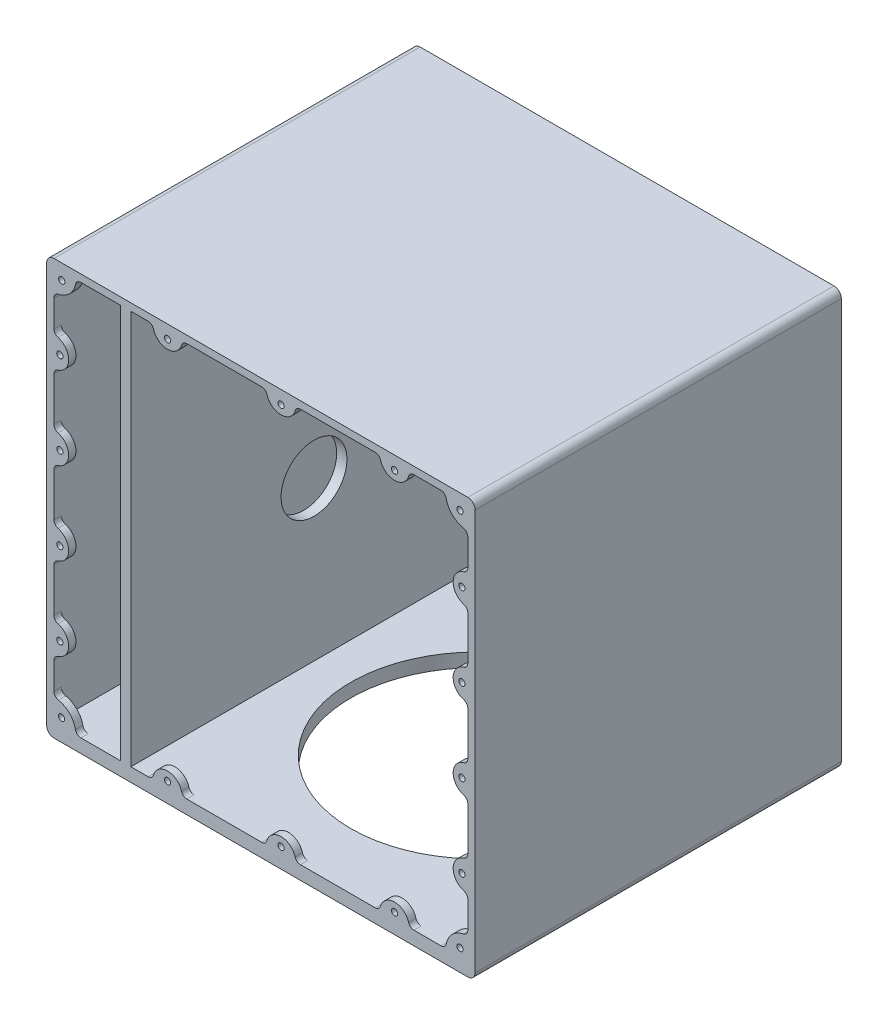
SolidWorks part; units mm, degrees
ref_plane "Front Plane" through (0, 0, 0) normal (0, 0, 1) x (1, 0, 0)
ref_plane "Top Plane" through (0, 0, 0) normal (0, 1, 0) x (1, 0, 0)
ref_plane "Right Plane" through (0, 0, 0) normal (1, 0, 0) x (0, 0, -1)
sketch "Sketch1" plane through (0, 0, 0) normal (0, 0, 1) x (1, 0, 0)
  line L8 (109, 48.0679) -> (82, 48.0679) construction
  line L11 (88.5, 124.8761) -> (88.5, -413.7188)
  line L12 (102.5, 124.8761) -> (102.5, -413.7188)
  line L13 (-12.5, 134.8761) -> (-12.5, -432.3088)
  line L14 (-12.5, -432.3088) -> (572.5, -432.3088)
  line L15 (572.5, 134.8761) -> (572.5, -432.3088)
  line L16 (-12.5, 134.8761) -> (572.5, 134.8761)
  line L17 (-2.5, 124.8761) -> (-2.5, -413.7188)
  line L18 (-2.5, -413.7188) -> (88.5, -413.7188)
  line L19 (562.5, 124.8761) -> (562.5, -413.7188)
  line L20 (-2.5, 124.8761) -> (88.5, 124.8761)
  line L24 (102.5, 124.8761) -> (562.5, 124.8761)
  line L26 (102.5, -413.7188) -> (562.5, -413.7188)
  dimension "D1" = 460
  dimension "D2" = 10
  dimension "D3" = 18.59
extrude "Boss-Extrude1" add sketch "Sketch1" along normal mid plane 500 contours L16 L13 L14 L15 L26 L12 L11 L18 L17 L20 L24 L19 region at (280, 126.7279, 0)
sketch "Sketch2" plane through (-12.5, 0, 0) normal (-1, 0, 0) x (0, 0, 1)
  circle A0 centre (0, -197.5) radius 45 construction
  circle A1 centre (0, 0) radius 55 construction
  circle A2 centre (0, -197.5) radius 45
  circle A3 centre (0, 0) radius 55
extrude "Cut-Extrude1" cut sketch "Sketch2" against normal up to surface (115 mm away) up to face at (102.5, -144.4214, 0)
sketch "Sketch3" plane through (-12.5, 0, 0) normal (-1, 0, 0) x (0, 0, 1)
  circle A0 centre (0, 0) radius 55 construction
  circle A1 centre (0, 0) radius 55
  circle A2 centre (0, 0) radius 70
  dimension "D1" = 15
extrude "Boss-Extrude2" add sketch "Sketch3" along normal mid plane 27 from offset 5 offset against normal yes
sketch "Sketch4" plane through (-21, 0, 0) normal (-1, 0, 0) x (0, 0, 1)
  circle A0 centre (0, 0) radius 70 construction
  circle A1 centre (0, 0) radius 70
sketch "Sketch5" plane through (-12.5, 0, 0) normal (-1, 0, 0) x (0, 0, 1)
  circle A0 centre (0, -197.5) radius 45 construction
  circle A1 centre (0, -197.5) radius 45
  circle A2 centre (0, -197.5) radius 70
  dimension "D1" = 25
sketch "Sketch7" plane through (0, 0, -250) normal (0, 0, -1) x (-1, 0, 0)
  line L0 (-572.5, 134.8761) -> (-572.5, -432.3088) construction
  line L1 (12.5, 134.8761) -> (-572.5, 134.8761) construction
  line L2 (12.5, 134.8761) -> (12.5, -432.3088) construction
  line L3 (12.5, -432.3088) -> (-572.5, -432.3088) construction
  line L4 (-572.5, 134.8761) -> (-572.5, -432.3088)
  line L5 (12.5, 134.8761) -> (-572.5, 134.8761)
  line L6 (12.5, 134.8761) -> (12.5, -432.3088)
  line L7 (12.5, -432.3088) -> (-572.5, -432.3088)
extrude "Boss-Extrude5" add sketch "Sketch7" against normal blind 10
fillet "Fillet1" radius 10 4 edges at (572.5, -432.3088, 0) (-12.5, -432.3088, 0) (-12.5, 134.8761, 0) (572.5, 134.8761, 0)
sketch "Sketch9" plane through (102.5, 0, 0) normal (1, 0, 0) x (0, 0, -1)
  circle A0 centre (0, 0) radius 55 construction
  circle A1 centre (0, 0) radius 55
extrude "Boss-Extrude7" add sketch "Sketch9" against normal blind 27 from offset 7
sketch "Sketch10" plane through (109.5, 0, 0) normal (1, 0, 0) x (0, 0, -1)
  circle A0 centre (0, 0) radius 55 construction
  circle A1 centre (0, 0) radius 55
sketch "Sketch11" plane through (102.5, 0, 0) normal (1, 0, 0) x (0, 0, -1)
  circle A0 centre (0, -197.5) radius 45 construction
  circle A1 centre (0, -197.5) radius 45
sketch "Sketch12" plane through (102.5, 0, 0) normal (1, 0, 0) x (0, 0, -1)
  circle A0 centre (0, -197.5) radius 45 construction
  circle A1 centre (0, -197.5) radius 45
extrude "Boss-Extrude8" add sketch "Sketch12" along normal blind 3 separate body
sketch "Sketch13" plane through (88.5, 0, 0) normal (-1, 0, 0) x (0, 0, 1)
  circle A0 centre (0, -197.5) radius 45 construction
  circle A1 centre (0, -197.5) radius 45
extrude "Boss-Extrude9" add sketch "Sketch13" along normal blind 4.5 separate body
sketch "Sketch14" plane through (0, 0, 0) normal (0, 0, 1) x (1, 0, 0)
  line L0 (0, 0) -> (19.9155, 0) construction
  line L1 (6, -70) -> (11, -70)
  line L2 (6, -70) -> (6, -49)
  line L3 (6, -49) -> (11, -49)
  line L4 (11, -70) -> (11, -49)
  dimension "D1" = 5
  dimension "D2" = 21
revolve "Revolve1" add sketch "Sketch14" angle 360 about L0
fillet "Fillet3" radius 0.5 1 edges at (6, 0, 49)
sketch "Sketch17" plane through (84, 0, 0) normal (-1, 0, 0) x (0, 0, 1)
  circle A1 centre (0, -197.5) radius 45
  circle A2 centre (0, -197.5) radius 45
  dimension "D1" = 0
extrude "Cut-Extrude5" cut sketch "Sketch17" against normal blind 58
sketch "Sketch18" plane through (82.5, 0, 0) normal (-1, 0, 0) x (0, 0, 1)
  circle A1 centre (0, 0) radius 55
  circle A2 centre (0, 0) radius 55
  dimension "D1" = 0
extrude "Cut-Extrude6" cut sketch "Sketch18" against normal blind 58
fillet "Fillet6" radius 1 1 edges at (-2.5, 70, 0)
fillet "Fillet7" radius 1 1 edges at (11, 0, 70)
sketch "Sketch20" plane through (0, -413.7188, 0) normal (0, 1, 0) x (1, 0, 0)
  circle A0 centre (325.6, 0) radius 77
  dimension "D1" = 154
extrude "Cut-Extrude7" cut sketch "Sketch20" against normal up to surface (18.59 mm away) up to face at (280, -432.3088, 0)
sketch "Sketch23" plane through (0, 0, 250) normal (0, 0, 1) x (1, 0, 0)
  line L0 (562.5, 124.8761) -> (562.5, -413.7188) construction
  line L1 (102.5, 124.8761) -> (562.5, 124.8761) construction
  line L2 (562.5, -144.4214) -> (-2.5, -144.4214) construction
  line L3 (-2.5, 124.8761) -> (-2.5, -413.7188) construction
  line L4 (280, 134.8761) -> (280, -432.3088) construction
  line L5 (-2.5, 134.8761) -> (562.5, 134.8761) construction
  line L6 (-2.5, -432.3088) -> (562.5, -432.3088) construction
  line L7 (102.5, 124.8761) -> (102.5, -413.7188) construction
  line L13 (132.5, 124.8761) -> (172.5, 124.8761)
  line L14 (287.5, 124.8761) -> (327.5, 124.8761)
  line L16 (442.5, 124.8761) -> (482.5, 124.8761)
  line L17 (532.5, 124.8761) -> (562.5, 124.8761)
  line L18 (562.5, 124.8761) -> (562.5, 94.8761)
  line L19 (562.5, 44.8761) -> (562.5, 4.8761)
  line L20 (562.5, -67.9889) -> (562.5, -107.9889)
  line L21 (562.5, -180.8539) -> (562.5, -220.8539)
  line L22 (562.5, -293.7188) -> (562.5, -333.7188)
  line L23 (562.5, -383.7188) -> (562.5, -413.7188)
  line L24 (562.5, -413.7188) -> (532.5, -413.7188)
  line L25 (482.5, -413.7188) -> (442.5, -413.7188)
  line L26 (327.5, -413.7188) -> (287.5, -413.7188)
  line L27 (172.5, -413.7188) -> (132.5, -413.7188)
  line L28 (27.5, -413.7188) -> (-2.5, -413.7188)
  line L29 (-2.5, -413.7188) -> (-2.5, -383.7188)
  line L30 (-2.5, -333.7188) -> (-2.5, -293.7188)
  line L31 (-2.5, -180.8539) -> (-2.5, -220.8539)
  line L32 (-2.5, -107.9889) -> (-2.5, -67.9889)
  line L33 (-2.5, 4.8761) -> (-2.5, 44.8761)
  line L34 (-2.5, 94.8761) -> (-2.5, 124.8761)
  line L35 (-2.5, 124.8761) -> (27.5, 124.8761)
  line L36 (132.5, 124.8761) -> (172.5, 124.8761)
  line L37 (287.5, 124.8761) -> (327.5, 124.8761)
  line L38 (482.5, 124.8761) -> (442.5, 124.8761)
  arc A0 (562.5, 94.8761) -> (532.5, 124.8761) centre (562.5, 124.8761) cw
  arc A1 (562.5, -383.7188) -> (532.5, -413.7188) centre (562.5, -413.7188) ccw
  arc A2 (-2.5, -383.7188) -> (27.5, -413.7188) centre (-2.5, -413.7188) cw
  arc A3 (-2.5, 94.8761) -> (27.5, 124.8761) centre (-2.5, 124.8761) ccw
  arc A4 (562.5, 44.8761) -> (562.5, 4.8761) centre (562.5, 24.8761) ccw
  arc A5 (562.5, -67.9889) -> (562.5, -107.9889) centre (562.5, -87.9889) ccw
  arc A6 (562.5, -180.8539) -> (562.5, -220.8539) centre (562.5, -200.8539) ccw
  arc A7 (562.5, -293.7188) -> (562.5, -333.7188) centre (562.5, -313.7188) ccw
  arc A8 (-2.5, -293.7188) -> (-2.5, -333.7188) centre (-2.5, -313.7188) cw
  arc A9 (-2.5, -180.8539) -> (-2.5, -220.8539) centre (-2.5, -200.8539) cw
  arc A10 (-2.5, -67.9889) -> (-2.5, -107.9889) centre (-2.5, -87.9889) cw
  arc A11 (-2.5, 44.8761) -> (-2.5, 4.8761) centre (-2.5, 24.8761) cw
  arc A12 (482.5, 124.8761) -> (442.5, 124.8761) centre (462.5, 124.8761) cw
  arc A13 (327.5, 124.8761) -> (287.5, 124.8761) centre (307.5, 124.8761) cw
  arc A14 (172.5, 124.8761) -> (132.5, 124.8761) centre (152.5, 124.8761) cw
  arc A15 (172.5, -413.7188) -> (132.5, -413.7188) centre (152.5, -413.7188) ccw
  arc A16 (327.5, -413.7188) -> (287.5, -413.7188) centre (307.5, -413.7188) ccw
  arc A17 (482.5, -413.7188) -> (442.5, -413.7188) centre (462.5, -413.7188) ccw
  line M3 (-2.5, 124.8761) -> (88.5, 124.8761)
  line M5 (88.5, -413.7188) -> (-2.5, -413.7188)
  line M6 (-2.5, -413.7188) -> (-2.5, 124.8761)
  line M7 (562.5, -413.7188) -> (102.5, -413.7188)
  line M9 (102.5, 124.8761) -> (562.5, 124.8761)
  line M10 (562.5, 124.8761) -> (562.5, -413.7188)
  dimension "D1" = 30
  dimension "D2" = 20
  dimension "D6" = 20
  dimension "D3" = 100
  dimension "D4" = 100
  dimension "D7" = 100
  dimension "D8" = 50
  dimension "D9" = 3
  dimension "D5" = 4
extrude "Boss-Extrude10" add sketch "Sketch23" against normal blind 10 contours A3 M6 M3 | A14 M9 | A13 M9 | A12 M9 | A0 M10 M9 | A4 M10 | A6 M10 | A1 M10 M7 | A17 M7 | A16 M7 | A2 M6 M5 | A8 M6 | A10 M6 | A11 M6 | A5 L20 | A7 L22 | A15 L27 | L31 A9 region at (307.5, -405.2306, 250) region at (462.5, -405.2306, 250) region at (549.7676, -400.9864, 250) region at (554.0117, -200.8539, 250) region at (554.0117, 24.8761, 250) region at (549.7676, 112.1437, 250) region at (462.5, 116.3878, 250) region at (307.5, 116.3878, 250) region at (152.5, 116.3878, 250) region at (10.2324, 112.1437, 250) region at (5.9883, 24.8761, 250) region at (5.9883, -87.9889, 250) region at (5.9883, -313.7188, 250) region at (10.2324, -400.9864, 250)
fillet "Fillet8" radius 7.5 36 edges at (132.5, 124.8761, 245) (172.5, 124.8761, 245) (27.5, 124.8761, 245) (-2.5, 94.8761, 245) (-2.5, 4.8761, 245) (-2.5, -107.9889, 245) (-2.5, -220.8539, 245) (-2.5, 44.8761, 245) (-2.5, -67.9889, 245) (-2.5, -180.8539, 245) (-2.5, -293.7188, 245) (-2.5, -333.7188, 245) (-2.5, -383.7188, 245) (27.5, -413.7188, 245) (132.5, -413.7188, 245) (172.5, -413.7188, 245) (287.5, -413.7188, 245) (327.5, -413.7188, 245) (482.5, -413.7188, 245) (442.5, -413.7188, 245) (532.5, -413.7188, 245) (562.5, -383.7188, 245) (562.5, -333.7188, 245) (562.5, -293.7188, 245) (562.5, -220.8539, 245) (562.5, -180.8539, 245) (562.5, -107.9889, 245) (562.5, -67.9889, 245) (562.5, 4.8761, 245) (562.5, 44.8761, 245) (562.5, 94.8761, 245) (287.5, 124.8761, 245) (327.5, 124.8761, 245) (482.5, 124.8761, 245) (532.5, 124.8761, 245) (442.5, 124.8761, 245)
hole_wizard "M10x1.5 Tapped Hole1" positions "Sketch27" profile "Sketch25" tap size "M10x1.5" standard "ANSI Metric"
sketch "Sketch27" plane through (0, 0, 250) normal (0, 0, 1) x (1, 0, 0)
  line L2 (18.7132, -392.5056) -> (-2.5, -413.7188) construction
  line L4 (307.5, -405.7188) -> (561.7445, -405.7188) construction
  line L6 (541.2868, -392.5056) -> (562.5, -413.7188) construction
  line L8 (152.5, 116.8761) -> (567.6087, 116.8761) construction
  line L10 (541.2868, 103.6628) -> (562.5, 124.8761) construction
  line L12 (18.7132, 103.6628) -> (-2.5, 124.8761) construction
  arc A0 (133.2582, 119.4215) -> (171.7418, 119.4215) centre (152.5, 124.8761) ccw construction
  arc A3 (2.9545, 5.6342) -> (2.9545, 44.1179) centre (-2.5, 24.8761) ccw construction
  arc A5 (26.8939, -407.7188) -> (3.5, -384.3249) centre (-2.5, -413.7188) ccw construction
  arc A6 (171.7418, -408.2643) -> (133.2582, -408.2643) centre (152.5, -413.7188) ccw construction
  arc A7 (326.7418, -408.2643) -> (288.2582, -408.2643) centre (307.5, -413.7188) ccw construction
  arc A8 (556.5, -384.3249) -> (533.1061, -407.7188) centre (562.5, -413.7188) ccw construction
  arc A9 (533.1061, 118.8761) -> (556.5, 95.4822) centre (562.5, 124.8761) ccw construction
  arc A11 (557.0455, 44.1179) -> (557.0455, 5.6342) centre (562.5, 24.8761) ccw construction
  arc A12 (3.5, 95.4822) -> (26.8939, 118.8761) centre (-2.5, 124.8761) ccw construction
  point P0 (152.5, 116.8761)
  point P6 (152.5, 104.8761)
  point P7 (307.5, 116.8761)
  point P9 (462.5, 116.8761)
  point P11 (554.5, 24.8761)
  point P20 (554.5, -87.9889)
  point P22 (554.5, -200.8539)
  point P24 (554.5, -313.7188)
  point P26 (462.5, -405.7188)
  point P35 (307.5, -405.7188)
  point P37 (152.5, -405.7188)
  point P39 (5.5, 24.8761)
  point P45 (17.5, 24.8761)
  point P46 (8.1066, 114.2694)
  point P48 (5.5, -87.9889)
  point P50 (5.5, -200.8539)
  point P52 (5.5, -313.7188)
  point P54 (7.9431, -402.9462)
  point P76 (152.5, -393.7188)
  point P88 (307.5, -393.7188)
  point P97 (551.8934, -403.1122)
  point P116 (551.8934, 114.2694)
  point P127 (542.5, 24.8761)
  dimension "D3" = 12
  dimension "D1" = 12
  dimension "D2" = 12
  dimension "D4" = 12
  dimension "D5" = 15
  dimension "D6" = 12
  dimension "D7" = 15
  dimension "D8" = 12
  dimension "D9" = 15
  dimension "D10" = 15
sketch "Sketch25" plane through (152.5, 116.8761, 250) normal (1, 0, 0) x (0, -1, 0)
  line L0 (0, 0) -> (0, 12.5537)
  line L1 (0, 12.5537) -> (4.25, 10)
  line L2 (4.25, 10) -> (4.25, 0)
  line L5 (4.25, 0) -> (0, 0)
  line L10 (0, 12.5537) -> (-4.25, 10) construction
  line L11 (0, -6.35) -> (0, 107.95) construction
  dimension "Tap Drill Dia." = 8.5
  dimension "Tap Drill Depth" = 10
  dimension "Drill Angle" = 118
cosmetic thread "Hole Thread1" parameters "D1"=20, "D2"=10
cosmetic thread "Hole Thread2" parameters "D1"=20, "D2"=10
cosmetic thread "Hole Thread3" parameters "D1"=20, "D2"=10
cosmetic thread "Hole Thread4" parameters "D1"=20, "D2"=10
cosmetic thread "Hole Thread5" parameters "D1"=20, "D2"=10
cosmetic thread "Hole Thread6" parameters "D1"=20, "D2"=10
cosmetic thread "Hole Thread7" parameters "D1"=20, "D2"=10
cosmetic thread "Hole Thread8" parameters "D1"=20, "D2"=10
cosmetic thread "Hole Thread10" parameters "D1"=20, "D2"=10
cosmetic thread "Hole Thread17" parameters "D1"=20, "D2"=10
cosmetic thread "Hole Thread18" parameters "D1"=20, "D2"=10
cosmetic thread "Hole Thread19" parameters "D1"=20, "D2"=10
cosmetic thread "Hole Thread20" parameters "D1"=20, "D2"=10
cosmetic thread "Hole Thread21" parameters "D1"=20, "D2"=10
cosmetic thread "Hole Thread22" parameters "D1"=20, "D2"=10
cosmetic thread "Hole Thread23" parameters "D1"=20, "D2"=10
cosmetic thread "Hole Thread24" parameters "D1"=20, "D2"=10
cosmetic thread "Hole Thread25" parameters "D1"=20, "D2"=10
sketch "Sketch28" plane through (0, -432.3088, 0) normal (0, -1, 0) x (1, 0, 0)
  circle A0 centre (325.6, 0) radius 172.9745
extrude "Cut-Extrude8" cut sketch "Sketch28" against normal up to surface (18.59 mm away) up to face at (337.3064, -413.7188, 191.1111)
hole_wizard "M16x2.0 Tapped Hole1" positions "Sketch29" profile "Sketch31" tap size "M16x2.0" standard "ANSI Metric"
sketch "Sketch29" plane through (102.5, 0, 0) normal (1, 0, 0) x (0, 0, -1)
  point P0 (42.2127, 47.6956)
  point P3 (62.615, -12.476)
  point P6 (20.7061, -60.2308)
  point P9 (-41.6053, -47.814)
  point P12 (-62.0077, 12.3577)
  point P15 (-20.0987, 60.1125)
sketch "Sketch31" plane through (102.5, 47.6956, -42.2127) normal (0, 1, 0) x (0, 0, -1)
  line L0 (0, 0) -> (0, 10.206)
  line L1 (0, 10.206) -> (7, 6)
  line L2 (7, 6) -> (7, 0)
  line L5 (7, 0) -> (0, 0)
  line L10 (0, 10.206) -> (-7, 6) construction
  line L11 (0, -6.35) -> (0, 107.95) construction
  dimension "Tap Drill Dia." = 14
  dimension "Tap Drill Depth" = 6
  dimension "Drill Angle" = 118
cosmetic thread "Hole Thread26" parameters "D1"=2, "D2"=16
cosmetic thread "Hole Thread27" parameters "D1"=2, "D2"=16
cosmetic thread "Hole Thread28" parameters "D1"=2, "D2"=16
cosmetic thread "Hole Thread29" parameters "D1"=2, "D2"=16
cosmetic thread "Hole Thread30" parameters "D1"=2, "D2"=16
cosmetic thread "Hole Thread31" parameters "D1"=2, "D2"=16
hole_wizard "M14x2.0 Tapped Hole1" positions "Sketch34" profile "Sketch33" tap size "M14x2.0" standard "ANSI Metric"
sketch "Sketch34" plane through (-12.5, 0, 0) normal (-1, 0, 0) x (0, 0, 1)
  point P0 (-0.2005, 65.0755)
  point P3 (56.2129, 32.7365)
  point P6 (56.4132, -32.2885)
  point P9 (0.2001, -64.9745)
  point P12 (-56.2133, -32.6354)
  point P15 (-56.4136, 32.3895)
sketch "Sketch33" plane through (-12.5, 65.0755, -0.2005) normal (0, 1, 0) x (0, 0, 1)
  line L0 (0, 0) -> (0, 8.6052)
  line L1 (0, 8.6052) -> (6, 5)
  line L2 (6, 5) -> (6, 0)
  line L5 (6, 0) -> (0, 0)
  line L10 (0, 8.6052) -> (-6, 5) construction
  line L11 (0, -6.35) -> (0, 107.95) construction
  dimension "Tap Drill Dia." = 12
  dimension "Tap Drill Depth" = 5
  dimension "Drill Angle" = 118
cosmetic thread "Hole Thread32" parameters "D1"=28, "D2"=14
cosmetic thread "Hole Thread33" parameters "D1"=28, "D2"=14
cosmetic thread "Hole Thread34" parameters "D1"=28, "D2"=14
cosmetic thread "Hole Thread37" parameters "D1"=28, "D2"=14
cosmetic thread "Hole Thread38" parameters "D1"=28, "D2"=14
cosmetic thread "Hole Thread39" parameters "D1"=28, "D2"=14
sketch "Sketch39" plane through (0, -432.3088, 0) normal (0, -1, 0) x (1, 0, 0)
  circle A0 centre (325.6, 0) radius 197 construction
  dimension "D1" = 394
hole_wizard "M16x2.0 Tapped Hole7" positions "Sketch54" profile "Sketch55" tap size "M16x2.0" standard "ANSI Metric"
sketch "Sketch54" plane through (0, -432.3088, 0) normal (0, -1, 0) x (-1, 0, 0)
  point P0 (-227.8622, 171.0448)
  point P3 (-520.1173, 31.1772)
  point P6 (-423.3378, -171.0448)
  point P9 (-240.5571, -177.6983)
  point P12 (-131.0827, -31.1772)
  point P15 (-410.6429, 177.6983)
sketch "Sketch55" plane through (227.8622, -432.3088, -171.0448) normal (1, 0, 0) x (0, 0, -1)
  line L0 (0, 0) -> (0, 9.206)
  line L1 (0, 9.206) -> (7, 5)
  line L2 (7, 5) -> (7, 0)
  line L5 (7, 0) -> (0, 0)
  line L10 (0, 9.206) -> (-7, 5) construction
  line L11 (0, -6.35) -> (0, 107.95) construction
  dimension "Tap Drill Dia." = 14
  dimension "Tap Drill Depth" = 5
  dimension "Drill Angle" = 118
cosmetic thread "Hole Thread53" parameters "D1"=32, "D2"=16
cosmetic thread "Hole Thread54" parameters "D1"=32, "D2"=16
cosmetic thread "Hole Thread55" parameters "D1"=32, "D2"=16
cosmetic thread "Hole Thread56" parameters "D1"=32, "D2"=16
cosmetic thread "Hole Thread57" parameters "D1"=32, "D2"=16
cosmetic thread "Hole Thread58" parameters "D1"=32, "D2"=16
